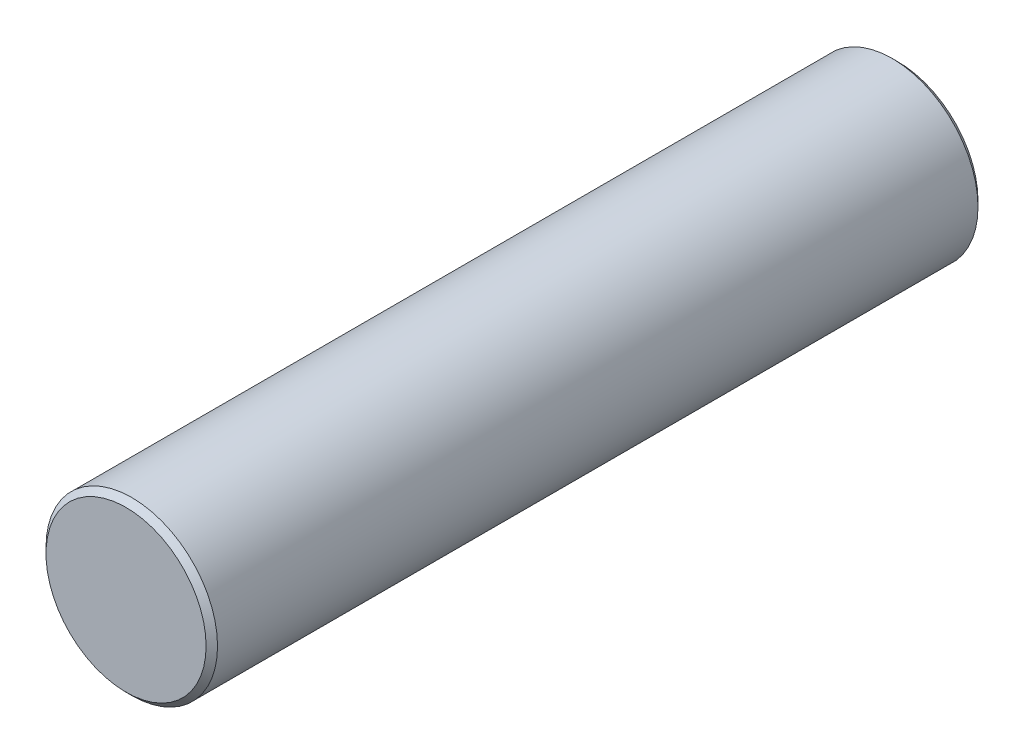
SolidWorks part; units mm, degrees
material "ASTM A36 Steel"
ref_plane "Front Plane" through (0, 0, 0) normal (0, 0, 1) x (1, 0, 0)
ref_plane "Top Plane" through (0, 0, 0) normal (0, 1, 0) x (1, 0, 0)
ref_plane "Right Plane" through (0, 0, 0) normal (1, 0, 0) x (0, 0, -1)
sketch "Sketch1" plane through (0, 0, 0) normal (0, 0, 1) x (1, 0, 0)
  circle A0 centre (0, 0) radius 30
  dimension "D1" = 60
extrude "Boss-Extrude1" add sketch "Sketch1" along normal blind 270
chamfer "Chamfer1" distance 2 angle 45 2 edges at (30, 0, 270) (30, 0, 0)
sketch "Sketch2" plane through (0, 0, 0) normal (0, 0, -1) x (-1, 0, 0)
  circle A0 centre (0, 0) radius 5
  dimension "D1" = 10
extrude "Cut-Extrude1" cut sketch "Sketch2" against normal blind 30
thread "Thread1" pitch 1.5 method extrude profile "Thread Profile1" start angle 0, offset 0, length 30, pitch 1.5, diameter 10
ref_plane "Plane1" through (5, 0, 0) normal (0, -1, 0) x (1, 0, 0)
sketch "Thread Profile1" plane through (5, 0, 0) normal (0, -1, 0) x (1, 0, 0)
  line L0 (0, 0) -> (0, 1.5) construction
  line L1 (0, 1.125) -> (-0.8119, 0.6563)
  line L2 (-0.8119, 0.6563) -> (-0.8119, 0.4688)
  line L3 (-0.8119, 0.4688) -> (0, 0)
  line L4 (-0.8119, 0.5625) -> (0, 0.5625) construction
  line L11 (0, 1.125) -> (0, 0)
  point P6 (0, 0)
  dimension "Pitch" = 1.5
  dimension "Profile_Angle" = 60
  dimension "Profile_Land" = 0.1875
  dimension "Profile_Height" = 0.8119
